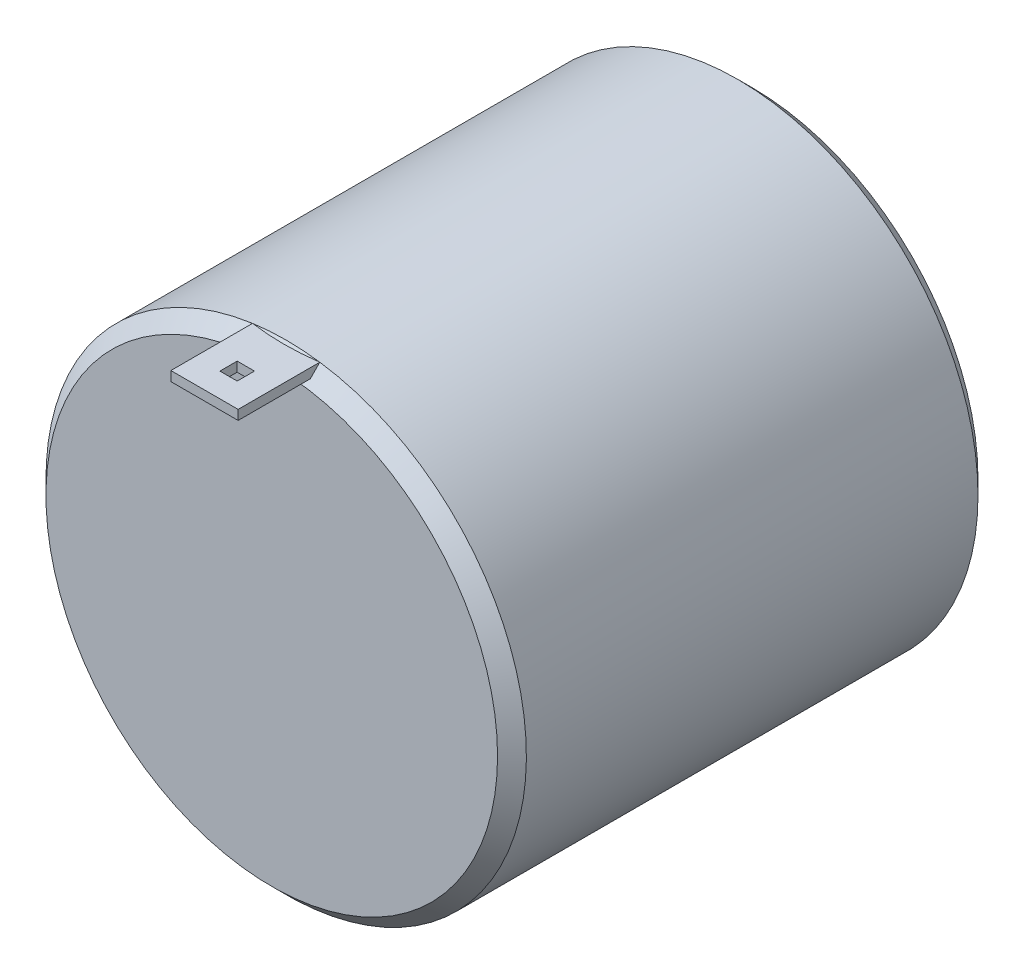
SolidWorks part; units mm, degrees
ref_plane "Front" through (0, 0, 0) normal (0, 0, 1) x (1, 0, 0)
ref_plane "Top" through (0, 0, 0) normal (0, 1, 0) x (1, 0, 0)
ref_plane "Right" through (0, 0, 0) normal (1, 0, 0) x (0, 0, -1)
sketch "Sketch1" plane through (0, 0, 0) normal (0, 0, 1) x (1, 0, 0)
  line L1 (0, 0) -> (50, 0) construction
  line L2 (0, 0) -> (0, 50) construction
  line L3 (0, 50) -> (50, 50) construction
  line L4 (50, 0) -> (50, 50) construction
  circle A0 centre (25, 25) radius 25
  dimension "D1" = 50
extrude "Boss-Extrude1" add sketch "Sketch1" along normal blind 50
chamfer "Chamfer1" distance 1.5 angle 45 2 edges at (50, 25, 0) (50, 25, 50)
sketch "Sketch2" plane through (0, 0, 50) normal (0, 0, 1) x (1, 0, 0)
  line L1 (21.5, 49.7538) -> (28.5, 49.7538)
  line L2 (21.5, 49.7538) -> (21.5, 48.7538)
  line L3 (21.5, 48.7538) -> (28.5, 48.7538)
  line L4 (28.5, 49.7538) -> (28.5, 48.7538)
  circle A0 centre (25, 25) radius 25 construction
  dimension "D1" = 7
  dimension "D2" = 1
extrude "Boss-Extrude2" add sketch "Sketch2" along normal blind 7 and the other way blind 10
sketch "Sketch3" plane through (0, 48.7538, 0) normal (0, -1, 0) x (1, 0, 0)
  line L0 (25, 54.5) -> (25, 57) construction
  line L1 (24.1, 54.5) -> (25.9, 54.5)
  line L2 (24.1, 54.5) -> (24.1, 52.7)
  line L3 (24.1, 52.7) -> (25.9, 52.7)
  line L4 (25.9, 54.5) -> (25.9, 52.7)
  line L5 (21.5, 57) -> (28.5, 57) construction
  dimension "D1" = 2.5
  dimension "D2" = 1.8
extrude "Cut-Extrude1" cut sketch "Sketch3" against normal blind 7
